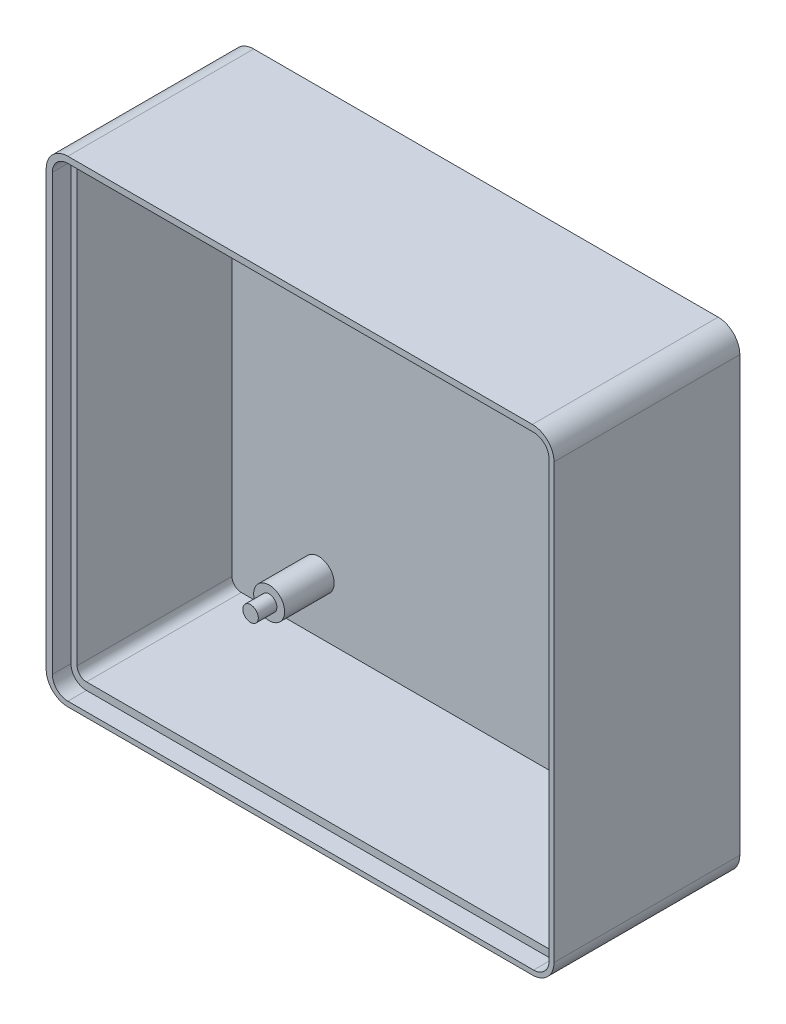
SolidWorks part; units mm, degrees
ref_plane "Plan de face" through (0, 0, 0) normal (0, 0, 1) x (1, 0, 0)
ref_plane "Plan de dessus" through (0, 0, 0) normal (0, 1, 0) x (1, 0, 0)
ref_plane "Plan de droite" through (0, 0, 0) normal (1, 0, 0) x (0, 0, -1)
sketch "Esquisse1" plane through (0, 0, 0) normal (0, 0, 1) x (1, 0, 0)
  line L1 (-32.8398, 17.6699) -> (42.1602, 17.6699)
  line L2 (-35.3398, 15.1699) -> (-35.3398, -54.8301)
  line L3 (-32.8398, -57.3301) -> (42.1602, -57.3301)
  line L4 (44.6602, 15.1699) -> (44.6602, -54.8301)
  arc A0 (-32.8398, 17.6699) -> (-35.3398, 15.1699) centre (-32.8398, 15.1699) ccw
  arc A1 (44.6602, 15.1699) -> (42.1602, 17.6699) centre (42.1602, 15.1699) ccw
  arc A2 (-35.3398, -54.8301) -> (-32.8398, -57.3301) centre (-32.8398, -54.8301) ccw
  arc A3 (42.1602, -57.3301) -> (44.6602, -54.8301) centre (42.1602, -54.8301) ccw
  dimension "D3" = 5
  dimension "D1" = 5
  dimension "D4" = 5
  dimension "D5" = 5
  dimension "D2" = 80
  dimension "D6" = 75
extrude "Extru.-Mince1" add sketch "Esquisse1" along normal blind 30 thin thin type mid plane wall 2
extrude "Boss.-Extru.1" add sketch "Esquisse1<2>" along normal blind 2
sketch "Esquisse1<2>" plane through (0, 0, 0) normal (0, 0, 1) x (1, 0, 0) same geometry as "Esquisse1"
sketch "Esquisse2" plane through (0, 0, 30) normal (0, 0, 1) x (1, 0, 0)
  line L0 (43.6602, -54.8301) -> (43.6602, 15.1699) construction
  line L1 (-32.8398, 17.6699) -> (42.3602, 17.6699)
  line L2 (-35.3398, 15.1699) -> (-35.3398, -55.0301)
  line L3 (-32.8398, -57.5301) -> (42.3602, -57.5301)
  line L4 (44.8602, 15.1699) -> (44.8602, -55.0301)
  line L5 (-32.8398, -56.3301) -> (42.1602, -56.3301) construction
  arc A0 (-32.8398, 17.6699) -> (-35.3398, 15.1699) centre (-32.8398, 15.1699) ccw
  arc A1 (44.8602, 15.1699) -> (42.3602, 17.6699) centre (42.3602, 15.1699) ccw
  arc A2 (42.3602, -57.5301) -> (44.8602, -55.0301) centre (42.3602, -55.0301) ccw
  arc A3 (-35.3398, -55.0301) -> (-32.8398, -57.5301) centre (-32.8398, -55.0301) ccw
  dimension "D5" = 5
  dimension "D6" = 5
  dimension "D7" = 5
  dimension "D8" = 5
  dimension "D3" = 1.2
  dimension "D4" = 1.2
extrude "Enlèv. mat.-Extru.1" cut sketch "Esquisse2" against normal blind 3
sketch "Esquisse3" plane through (0, 0, 2) normal (0, 0, 1) x (1, 0, 0)
  line L0 (42.3602, 17.6699) -> (-32.8398, 17.6699) construction
  line L1 (-35.3398, 15.1699) -> (-35.3398, -55.0301) construction
  line L2 (44.8602, -55.0301) -> (44.8602, 15.1699) construction
  line L3 (-35.3398, 15.1699) -> (-35.3398, -55.0301) construction
  line L4 (-32.8398, -57.5301) -> (42.3602, -57.5301) construction
  circle A0 centre (-20.3398, 7.6699) radius 2.5
  circle A1 centre (29.8602, 7.6699) radius 2.5
  circle A2 centre (29.8602, -47.5301) radius 2.5
  circle A3 centre (-20.3398, -47.5301) radius 2.5
  dimension "D1" = 5
  dimension "D2" = 5
  dimension "D3" = 5
  dimension "D4" = 5
  dimension "D5" = 10
  dimension "D6" = 15
  dimension "D7" = 10
  dimension "D8" = 15
  dimension "D9" = 15
  dimension "D10" = 10
  dimension "D11" = 15
  dimension "D12" = 10
  dimension "D13" = 55.2
  dimension "D14" = 50.2
extrude "Boss.-Extru.2" add sketch "Esquisse3" along normal blind 8
sketch "Esquisse4" plane through (0, 0, 10) normal (0, 0, 1) x (1, 0, 0)
  circle A0 centre (-20.3398, 7.6699) radius 1.25
  circle A1 centre (29.8602, 7.6699) radius 1.25
  circle A2 centre (-20.3398, -47.5301) radius 1.25
  circle A3 centre (29.6602, -47.3301) radius 1.25
  dimension "D1" = 2.5
  dimension "D2" = 2.5
  dimension "D3" = 2.5
  dimension "D4" = 2.5
extrude "Boss.-Extru.3" add sketch "Esquisse4" along normal blind 3
